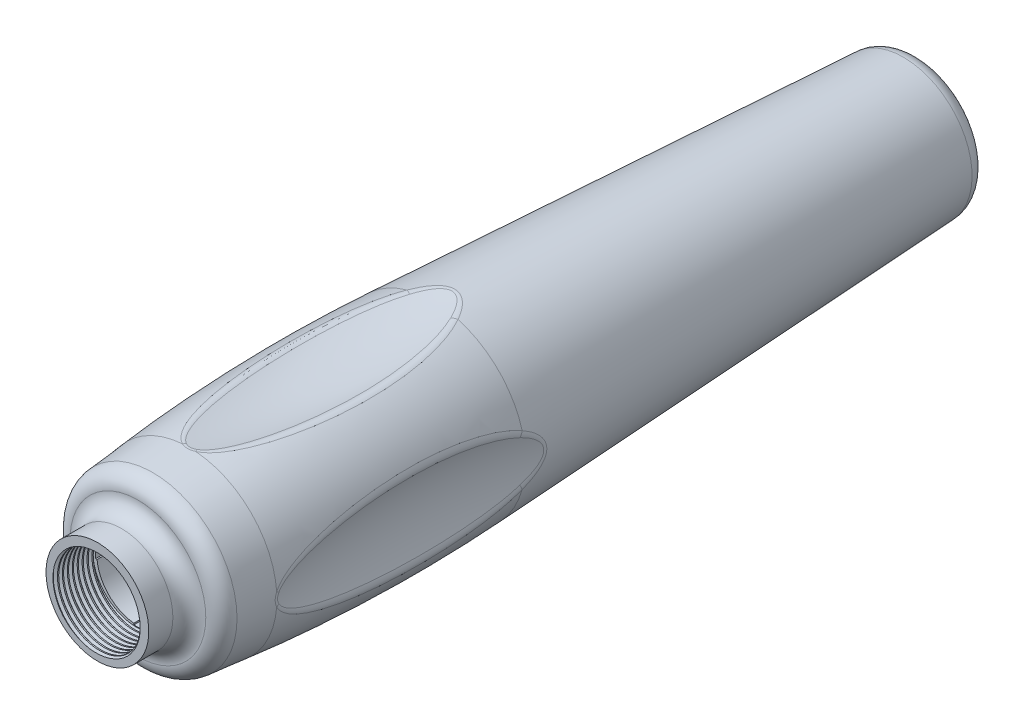
SolidWorks part; units mm, degrees
ref_plane "Ön Düzlem" through (0, 0, 0) normal (0, 0, 1) x (1, 0, 0)
ref_plane "Üst Düzlem" through (0, 0, 0) normal (0, 1, 0) x (1, 0, 0)
ref_plane "Sağ Düzlem" through (0, 0, 0) normal (1, 0, 0) x (0, 0, -1)
sketch "Sketch1" plane through (0, 0, 0) normal (0, 0, 1) x (1, 0, 0)
  circle A0 centre (0, 0) radius 5
  circle A1 centre (0, 0) radius 11.25
  dimension "D1" = 10
  dimension "D2" = 22.5
extrude "Boss-Extrude1" add sketch "Sketch1" along normal blind 51 and the other way blind 35
sketch "Sketch2" plane through (0, 0, -35) normal (0, 0, -1) x (-1, 0, 0)
  circle A0 centre (0, 0) radius 11.25
extrude "Boss-Extrude2" add sketch "Sketch2" along normal blind 9
sketch "Sketch3" plane through (0, 0, -44) normal (0, 0, -1) x (-1, 0, 0)
  line L0 (-2, 4.5) -> (-3, 3.5)
  line L1 (-3, 2.5) -> (3, 2.5)
  line L2 (-3, 2.5) -> (-3, 3.5)
  line L3 (-2, 4.5) -> (2, 4.5)
  line L4 (3, 2.5) -> (3, 3.5)
  line L5 (3, 3.5) -> (2, 4.5)
  point P4 (0, 2.5)
  dimension "D1" = 6
  dimension "D3" = 2.5
  dimension "D4" = 4
  dimension "D5" = 45
extrude "Cut-Extrude1" cut sketch "Sketch3" against normal blind 6
sketch "Sketch4" plane through (0, 0, -44) normal (0, 0, -1) x (-1, 0, 0)
  line L1 (-5, -1) -> (5, -1)
  line L2 (-5, -1) -> (-5, -3.5)
  line L3 (-5, -3.5) -> (5, -3.5)
  line L4 (5, -1) -> (5, -3.5)
  point P4 (0, -3.5)
  dimension "D1" = 10
  dimension "D2" = 2.5
  dimension "D3" = 1
extrude "Cut-Extrude2" cut sketch "Sketch4" against normal blind 5 from offset 2.5 offset against normal yes
sketch "Sketch5" plane through (0, 0, -44) normal (0, 0, -1) x (-1, 0, 0)
  circle A0 centre (0, -3.5) radius 2.5
  dimension "D1" = 5
  dimension "D2" = 3.5
extrude "Cut-Extrude3" cut sketch "Sketch5" against normal blind 7.5
sketch "Sketch6" plane through (0, 0, 51) normal (0, 0, 1) x (1, 0, 0)
  line L0 (0.5, 4.9) -> (-0.5, 4.9)
  line L1 (-4.9, 0.5) -> (-5.15, 0.5)
  line L2 (-4.9, 0.5) -> (-4.9, -0.5)
  line L3 (-4.9, -0.5) -> (-5.15, -0.5)
  line L4 (-5.15, 0.5) -> (-5.15, -0.5)
  line L5 (0.5, 4.9) -> (0.5, 5.15)
  line L6 (0.5, 5.15) -> (-0.5, 5.15)
  line L7 (-0.5, 4.9) -> (-0.5, 5.15)
  line L8 (4.9, -0.5) -> (4.9, 0.5)
  line L9 (4.9, -0.5) -> (5.15, -0.5)
  line L10 (5.15, -0.5) -> (5.15, 0.5)
  line L11 (4.9, 0.5) -> (5.15, 0.5)
  line L12 (-0.5, -4.9) -> (0.5, -4.9)
  line L13 (-0.5, -4.9) -> (-0.5, -5.15)
  line L14 (-0.5, -5.15) -> (0.5, -5.15)
  line L15 (0.5, -4.9) -> (0.5, -5.15)
  point P4 (-4.9, 0)
  point P21 (0, 0)
  dimension "D1" = 1
  dimension "D2" = 0.25
  dimension "D3" = 4.9
  dimension "D4" = 4
extrude "Cut-Extrude4" cut sketch "Sketch6" against normal blind 10
sketch "Sketch7" plane through (0, 0, 51) normal (0, 0, 1) x (1, 0, 0)
  line L0 (-11.25, 11.25) -> (11.25, -11.25) construction
  line L1 (-11.25, 11.25) -> (11.25, 11.25)
  line L2 (-11.25, 11.25) -> (-11.25, -11.25)
  line L3 (-11.25, -11.25) -> (11.25, -11.25)
  line L4 (11.25, 11.25) -> (11.25, -11.25)
  circle A0 centre (0, 0) radius 7.5
  point P4 (0, 0)
  dimension "D3" = 15
  dimension "D1" = 22.5
  dimension "D2" = 22.5
extrude "Boss-Extrude3" add sketch "Sketch7" against normal blind 55
sketch "Sketch11" plane through (0, 0, 51) normal (0, 0, 1) x (1, 0, 0)
  circle A0 centre (0, 0) radius 5.5
  circle A1 centre (0, 0) radius 6.25
  dimension "D1" = 12.5
  dimension "D2" = 11
extrude "Boss-Extrude4" add sketch "Sketch11" along normal blind 5
thread "Thread1" pitch 0.6 start angle 0, offset 1, length 6, pitch 0.6, diameter 11
ref_plane "Plane1" through (-5.5, 0, 57) normal (0, -1, 0) x (-1, 0, 0)
sketch "Thread Profile1" plane through (-5.5, 0, 57) normal (0, -1, 0) x (-1, 0, 0)
  line L0 (0, 0) -> (0, 0.6) construction
  line L11 (0, 0) -> (0, 0.525)
  line L12 (0, 0.525) -> (-0.3248, 0.3375)
  line L13 (-0.3248, 0.3375) -> (-0.3248, 0.1875)
  line L15 (-0.3248, 0.1875) -> (0, 0)
  line L17 (-0.3248, 0.2625) -> (0, 0.2625) construction
  point P2 (0, 0)
  dimension "Pitch" = 0.6
  dimension "Profile_Angle" = 60
  dimension "Profile_Land" = 0.15
  dimension "Profile_Height" = 0.3248
sketch "Sketch14" plane through (11.25, 0, 0) normal (1, 0, 0) x (0, 0, -1)
  line L1 (-70.4093, 18.7396) -> (-55.9318, 18.7396)
  line L2 (-70.4093, 18.7396) -> (-70.4093, -13.801)
  line L3 (-70.4093, -13.801) -> (-55.9318, -13.801)
  line L4 (-55.9318, 18.7396) -> (-55.9318, -13.801)
extrude "Cut-Extrude5" cut sketch "Sketch14" against normal blind 30
sketch "Sketch15" plane through (0, 0, 0) normal (0, 1, 0) x (1, 0, 0)
  line L0 (-8.2, 44.75) -> (-12.1175, -30)
  line L1 (-12.1175, -30) -> (-8.2138, -70)
  line L2 (11.25, 44) -> (-11.25, 44) construction
  line L3 (-8.2, 44.75) -> (-53.2, 44.75)
  line L4 (-53.2, 44.75) -> (-53.2, -813.9012)
  line L5 (0, 0) -> (0, 16.5551) construction
  line L6 (-8.2138, -70) -> (-14.2138, -70)
  line L7 (-14.2138, -70) -> (-53.2, -813.9012)
  dimension "D1" = 8.2
  dimension "D2" = 0.75
  dimension "D3" = 45
  dimension "D4" = 87
  dimension "D5" = 6
  dimension "D6" = 30
  dimension "D7" = 40
revolve "Cut-Revolve2" cut sketch "Sketch15" angle 360 about L5
ref_plane "Plane2" through (0, 22.25, 0) normal (0, 1, 0) x (1, 0, 0)
sketch "Sketch17" plane through (0, 22.25, 0) normal (0, 1, 0) x (1, 0, 0)
  line L0 (0, 0) -> (0, -1000) construction
  line L1 (0, 8.75) -> (-10, -8.75) construction
  line L2 (-10, -8.75) -> (10, -8.75) construction
  line L3 (10, -8.75) -> (-12.5, -35.75) construction
  line L4 (-12.5, -35.75) -> (12.5, -35.75) construction
  line L5 (12.5, -35.75) -> (-7.5, -62.75) construction
  line L6 (-7.5, -62.75) -> (7.5, -62.75) construction
  line L7 (7.5, -62.75) -> (0, -80.25) construction
  line L8 (0, 8.75) -> (0, -80.25)
  spline S0 degree 3 poles (0, 8.75) (-11.4173, -3.3834) (-15.5618, -36.0221) (-7.524, -66.5319) (0, -80.25) knots 0 0 0 0 0.50412 1 1 1 1
  point P5 (0, -8.75)
  point P12 (0, -35.75)
  point P13 (0, -62.75)
  dimension "D1" = 1000
  dimension "D2" = 17.5
  dimension "D3" = 17.5
  dimension "D4" = 27
  dimension "D5" = 27
  dimension "D6" = 15
  dimension "D7" = 25
  dimension "D8" = 20
  dimension "D9" = 8.75
revolve "Cut-Revolve3" cut sketch "Sketch17" angle 360 about L8
pattern_circular "CirPattern1" count 4 over 360 about axis through (0, 0, 56) along (0, 0, -1) of "Cut-Revolve3"
fillet "Fillet11" radius 198 4 edges at (-8.5684, -8.5684, 30) (8.5684, -8.5684, 30) (-8.5684, 8.5684, 30) (8.5684, 8.5684, 30)
fillet "Fillet13" radius 1.25 16 edges at (-10.6715, 0.0841, 44.8133) (-10.5803, -3.0827, 40.8371) (-11.2081, 0.0551, 12.6513) (-2.9765, -10.5862, 41.1384) (-0.0841, -10.6715, 44.8133) (3.0827, -10.5803, 40.8371) (-0.0551, -11.2081, 12.6513) (10.5803, 3.0827, 40.8371) (11.2081, -0.0551, 12.6513) (10.5862, -2.9765, 41.1384) (10.6715, -0.0841, 44.8133) (2.9765, 10.5862, 41.1384) (0.0841, 10.6715, 44.8133) (-3.0827, 10.5803, 40.8371) (0.0551, 11.2081, 12.6513) (-10.5862, 2.9765, 41.1384)
fillet "Fillet14" radius 2 2 edges at (10.068, 0, 51) (6.25, 0, 51)
fillet "Fillet15" radius 2 1 edges at (-8.2393, 0, -44)
